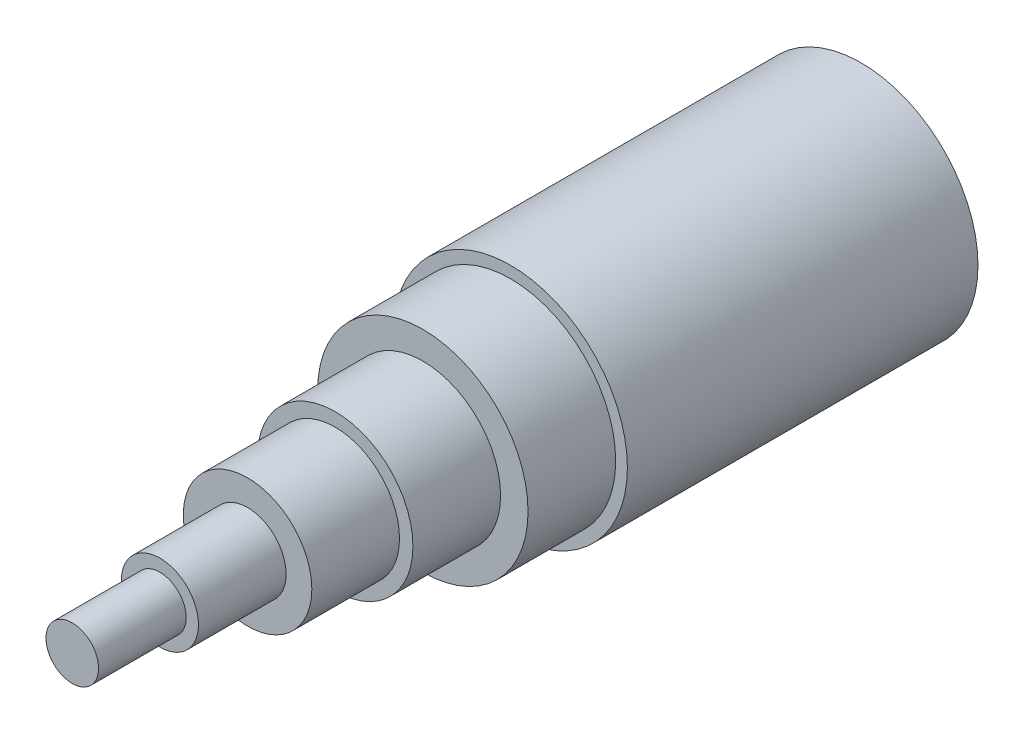
SolidWorks part; units mm, degrees
ref_plane "Front Plane" through (0, 0, 0) normal (0, 0, 1) x (1, 0, 0)
ref_plane "Top Plane" through (0, 0, 0) normal (0, 1, 0) x (1, 0, 0)
ref_plane "Right Plane" through (0, 0, 0) normal (1, 0, 0) x (0, 0, -1)
sketch "Sketch1" plane through (0, 0, 0) normal (0, 0, 1) x (1, 0, 0)
  circle A0 centre (0, 0) radius 1
  dimension "D1" = 2
extrude "Boss-Extrude1" add sketch "Sketch1" along normal blind 3
sketch "Sketch2" plane through (0, 0, 3) normal (0, 0, 1) x (1, 0, 0)
  circle A0 centre (0, 0) radius 0.9
  circle A1 centre (0, 0) radius 0.33
  circle A2 centre (0, 0) radius 0.55
  circle A3 centre (0, 0) radius 0.665
  circle A4 centre (0, 0) radius 0.225
  dimension "D1" = 1.8
  dimension "D2" = 0.66
  dimension "D3" = 1.1
  dimension "D4" = 1.33
  dimension "D5" = 0.45
extrude "Boss-Extrude2" add sketch "Sketch2" along normal blind 3 contours A1 region at (-0.3207, 0, 3)
extrude "Boss-Extrude3" add sketch "Sketch2<3>" along normal blind 2.25 contours A2 A1 region at (-0.5344, 0, 3)
sketch "Sketch2<3>" plane through (0, 0, 3) normal (0, 0, 1) x (1, 0, 0) same geometry as "Sketch2"
extrude "Boss-Extrude4" add sketch "Sketch2<4>" along normal blind 1.5 contours A3 A2 region at (-0.6462, 0, 3)
sketch "Sketch2<4>" plane through (0, 0, 3) normal (0, 0, 1) x (1, 0, 0) same geometry as "Sketch2"
extrude "Boss-Extrude6" add sketch "Sketch2<6>" along normal blind 0.75 contours A0 A3 region at (-0.8745, 0, 3)
sketch "Sketch2<6>" plane through (0, 0, 3) normal (0, 0, 1) x (1, 0, 0) same geometry as "Sketch2"
extrude "Boss-Extrude7" add sketch "Sketch2<7>" along normal blind 3.75 contours A4 region at (0, 0, 3)
sketch "Sketch2<7>" plane through (0, 0, 3) normal (0, 0, 1) x (1, 0, 0) same geometry as "Sketch2"
